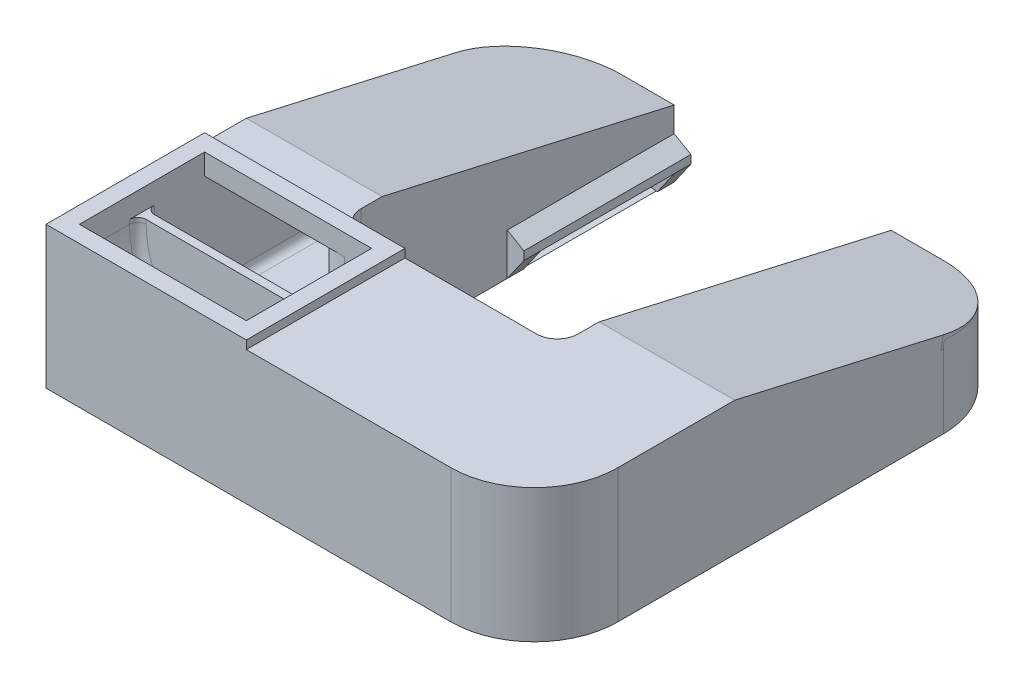
SolidWorks part; units mm, degrees
ref_plane "Front Plane" through (0, 0, 0) normal (0, 0, 1) x (1, 0, 0)
ref_plane "Top Plane" through (0, 0, 0) normal (0, 1, 0) x (1, 0, 0)
ref_plane "Right Plane" through (0, 0, 0) normal (1, 0, 0) x (0, 0, -1)
sketch "Sketch1" plane through (0, 0, 0) normal (0, 1, 0) x (1, 0, 0)
  line L0 (-13, 40) -> (-13, 0)
  line L1 (-13, 0) -> (13, 0)
  line L2 (13, 0) -> (13, 40)
  line L3 (13, 40) -> (19.25, 40)
  line L4 (29.25, 30) -> (29.25, -9)
  line L5 (19.25, -19) -> (-29.25, -19)
  line L6 (-29.25, -19) -> (-29.25, 30)
  line L7 (-19.25, 40) -> (-13, 40)
  arc A0 (19.25, 40) -> (29.25, 30) centre (19.25, 30) cw
  arc A1 (-29.25, 30) -> (-19.25, 40) centre (-19.25, 30) cw
  arc A2 (29.25, -9) -> (19.25, -19) centre (19.25, -9) cw
  point P11 (29.25, 40)
  point P14 (-29.25, 40)
  dimension "D7" = 10
  dimension "D8" = 10
  dimension "D1" = 26
  dimension "D2" = 13
  dimension "D3" = 40
  dimension "D4" = 16.25
  dimension "D5" = 16.25
  dimension "D6" = 19
extrude "Boss-Extrude1" add sketch "Sketch1" along normal blind 2
sketch "Sketch2" plane through (0, 2, 0) normal (0, 1, 0) x (1, 0, 0)
  line L0 (-29.25, 30) -> (-29.25, -19)
  line L1 (-29.25, -19) -> (19.25, -19)
  line L2 (-19.25, 40) -> (-13, 40)
  line L3 (-13, 40) -> (-13, 0)
  line L4 (-13, 0) -> (13, 0)
  line L5 (13, 0) -> (13, 40)
  line L6 (13, 40) -> (19.25, 40)
  line L7 (29.25, 30) -> (29.25, -9)
  line L8 (27.25, 30) -> (27.25, -9)
  line L9 (-27.25, -17) -> (19.25, -17)
  line L10 (-27.25, 30) -> (-27.25, -17)
  line L11 (-19.25, 38) -> (-15, 38)
  line L12 (-15, 38) -> (-15, -2)
  line L13 (-15, -2) -> (15, -2)
  line L14 (15, -2) -> (15, 38)
  line L15 (15, 38) -> (19.25, 38)
  arc A0 (-19.25, 40) -> (-29.25, 30) centre (-19.25, 30) ccw
  arc A1 (19.25, -19) -> (29.25, -9) centre (19.25, -9) ccw
  arc A2 (19.25, 40) -> (29.25, 30) centre (19.25, 30) cw
  arc A3 (19.25, 38) -> (27.25, 30) centre (19.25, 30) cw
  arc A4 (19.25, -17) -> (27.25, -9) centre (19.25, -9) ccw
  arc A5 (-19.25, 38) -> (-27.25, 30) centre (-19.25, 30) ccw
  dimension "D1" = 2
extrude "Boss-Extrude2" add sketch "Sketch2" along normal blind 14
sketch "Sketch3" plane through (0, 2, 0) normal (0, 1, 0) x (1, 0, 0)
  line L0 (-27.25, 30) -> (-27.25, -17) construction
  line L1 (-27.25, -9) -> (-7.25, -9)
  line L11 (15, -2) -> (-15, -2) construction
  line L15 (-7.25, -9) -> (-7.25, -2)
  line L16 (-27.25, -10) -> (-6.25, -10)
  line L18 (-7.25, -2) -> (15, -2)
  line L19 (-27.25, -9) -> (-27.25, -10)
  line L21 (-6.25, -10) -> (7, -10)
  line L23 (-27.25, -17) -> (19.25, -17) construction
  arc A0 (15, -2) -> (7, -10) centre (7, -2) cw
  dimension "D1" = 20
  dimension "D2" = 7
  dimension "D4" = 1
  dimension "D5" = 1
extrude "Boss-Extrude3" add sketch "Sketch3" along normal up to surface (14 mm away) up to face at (1.9383, 16, -15.9156)
fillet "Fillet1" radius 7 2 edges at (-7.25, 2, 5.5) (-17.25, 2, 9)
fillet "Fillet9" radius 12 1 edges at (-27.25, 2, 13.5)
fillet "Fillet6" radius 2.5 2 edges at (13, 8, 0) (-13, 8, 0)
fillet "Fillet7" radius 4.5 1 edges at (-15, 9, 2)
fillet "Fillet8" radius 1 22 edges at (-7.25, 12.5, 2) (-8.1161, 5.6273, 2) (-12.9756, 2.117, 1.2579) (12.6569, 2, 7.6569) (15, 2, -18) (17.125, 2, -38) (24.9069, 2, -35.6569) (27.25, 2, -10.5) (24.9069, 2, 14.6569) (2, 2, 17) (-4.125, 2, 10) (-24.9069, 2, -35.6569) (-17.125, 2, -38) (-15, 2, -20.25) (-14.8084, 2, -1.201) (-27.25, 2, -14) (-27.25, 15, 17) (-23.7353, 5.5147, 17) (-27.25, 15, 10) (-23.7353, 5.5147, 10) (-27.25, 12.5, 9) (-27.25, 4.0503, 6.9497)
sketch "Sketch4" plane through (0, 16, 0) normal (0, 1, 0) x (1, 0, 0)
  line L1 (-10.5, -2) -> (-27.25, -2)
  line L2 (-7.25, -10) -> (-7.25, -17)
  line L3 (-26.25, -17) -> (19.25, -17) construction
  line L6 (-15, 2.5) -> (-15, 38)
  line L7 (-15, 38) -> (-19.25, 38)
  line L8 (-27.25, 30) -> (-27.25, -2)
  line L9 (-7.25, -17) -> (19.25, -17)
  line L10 (27.25, -9) -> (27.25, 30)
  line L11 (19.25, 38) -> (15, 38)
  line L12 (15, 38) -> (15, -2)
  line L13 (7, -10) -> (-7.25, -10)
  line L14 (-26.25, -10) -> (7, -10) construction
  line L15 (-7.25, -3) -> (-7.25, -9) construction
  arc A1 (7, -10) -> (15, -2) centre (7, -2) ccw
  arc A2 (-19.25, 38) -> (-27.25, 30) centre (-19.25, 30) ccw
  arc A3 (19.25, 38) -> (27.25, 30) centre (19.25, 30) cw
  arc A4 (19.25, -17) -> (27.25, -9) centre (19.25, -9) ccw
  arc A6 (-15, 2.5) -> (-10.5, -2) centre (-10.5, 2.5) ccw
  arc A7 (-13.5682, -0.7918) -> (-10.5, -2) centre (-10.5, 2.5) ccw construction
extrude "Boss-Extrude4" add sketch "Sketch4" against normal blind 1.5
sketch "Sketch5" plane through (0, 16, 0) normal (0, 1, 0) x (1, 0, 0)
  line L0 (19.25, -17) -> (-15.25, -17) construction
  line L1 (-27.25, -2) -> (-7.25, -2)
  line L2 (-27.25, -2) -> (-27.25, -17)
  line L3 (-27.25, -17) -> (-7.25, -17)
  line L4 (-7.25, -2) -> (-7.25, -17)
  line L5 (-7.25, -10) -> (-7.25, -17) construction
extrude "Cut-Extrude1" cut sketch "Sketch5" against normal blind 1.5
sketch "Sketch6" plane through (0, 16, 0) normal (0, 1, 0) x (1, 0, 0)
  line L0 (-29.25, -19) -> (19.25, -19) construction
  line L1 (-27.25, -17) -> (-7.25, -17)
  line L2 (-27.25, -17) -> (-27.25, -2)
  line L3 (-27.25, -2) -> (-7.25, -2)
  line L4 (-7.25, -17) -> (-7.25, -2)
  line L5 (-5.25, -19) -> (-29.25, -19)
  line L6 (-5.25, -19) -> (-5.25, 0)
  line L7 (-5.25, 0) -> (-29.25, 0)
  line L8 (-29.25, -19) -> (-29.25, 0)
  dimension "D1" = 2
  dimension "D2" = 2
  dimension "D3" = 2
extrude "Boss-Extrude5" add sketch "Sketch6" along normal blind 1
ref_plane "Plane1" through (0, 0, -30) normal (0, 0, -1) x (-1, 0, 0)
sketch "Sketch7" plane through (0, 0, -30) normal (0, 0, -1) x (-1, 0, 0)
  line L0 (-13, 2) -> (0, 0) construction
  line L1 (-13, 0) -> (-13, 16) construction
  line L2 (0, 0) -> (13, 2) construction
  line L3 (13, 16) -> (13, 0) construction
  line L4 (-19.25, 0) -> (-13, 0) construction
  line L5 (10.5, 0) -> (13, 0) construction
  line L6 (19.25, 0) -> (29.25, 0) construction
  line L7 (26.1529, 2) -> (8.6205, -0.6973)
  line L8 (8.6205, -0.6973) -> (8.0123, 3.2562)
  line L9 (8.0123, 3.2562) -> (25.5447, 5.9535)
  line L10 (25.5447, 5.9535) -> (26.1529, 2)
  dimension "D1" = 2
  dimension "D2" = 2
  dimension "D3" = 2
  dimension "D4" = 4
  dimension "D5" = 2
extrude "Cut-Extrude2" cut sketch "Sketch7" against normal blind 8
sketch "Sketch9" plane through (-13, 0, 0) normal (1, 0, 0) x (0, 0, -1)
  line L0 (5, 16) -> (40, 8)
  line L1 (2.5, 16) -> (40, 16) construction
  line L2 (40, 16) -> (40, 0) construction
  line L3 (40, 8) -> (40, 16)
  line L4 (40, 16) -> (5, 16)
  dimension "D1" = 35
extrude "Cut-Extrude3" cut sketch "Sketch9" against normal through all
sketch "Sketch10" plane through (0, 16.2917, -3.7238) normal (0, 0.9749, -0.2228) x (1, 0, 0)
  line L0 (-29.25, 26.9538) -> (-29.25, 1.3091)
  line L1 (-29.25, 1.3091) -> (-13, 1.3091)
  line L2 (-13, 1.3091) -> (-13, 37.2117)
  line L3 (-13, 1.3091) -> (-13, 37.2117) construction
  line L4 (-13, 37.2117) -> (-19.25, 37.2117)
  line L5 (-13, 37.2117) -> (-13, 38.9943) construction
  arc A1 (-19.25, 37.2117) -> (-29.25, 26.9538) centre (-19.1042, 27.0664) ccw
  ellipse E0 centre (-19.25, 26.9538) end of major axis (-19.25, 37.2117) minor radius 10 (-19.25, 37.2117) -> (-29.25, 26.9538) ccw construction
extrude "Boss-Extrude6" add sketch "Sketch10" against normal blind 1.5
sketch "Sketch11" plane through (-0.3041, -1.9767, 0) normal (0.1521, 0.9884, 0) x (0.9884, -0.1521, 0)
  line L0 (-27.3893, 30) -> (-12.8488, 30)
  line L1 (-19.3893, 38) -> (-12.8488, 38)
  line L2 (-12.8488, 30) -> (-12.8488, 38)
  line L3 (-19.4823, 38) -> (-15.2817, 38) construction
  arc A0 (-27.3893, 30) -> (-19.3893, 38) centre (-19.3893, 30) cw
extrude "Cut-Extrude4" cut sketch "Sketch11" along normal blind 4
mirror "Mirror2" about plane through (0, 0, 0) normal (1, 0, 0) of "Cut-Extrude4", "Boss-Extrude6", "Cut-Extrude3", "Cut-Extrude2"
sketch "Sketch12" plane through (0, 0, -38) normal (0, 0, 1) x (1, 0, 0)
  line L0 (-13, 4.0235) -> (-11, 2.8688)
  line L1 (-11, 2.8688) -> (-11, 3.8688)
  line L2 (-11, 3.8688) -> (-13, 5.0235)
  line L3 (-13, 5.0235) -> (-13, 4.0235)
  line L4 (-13, 0) -> (-13, 4.0235) construction
  dimension "D1" = 2
  dimension "D2" = 1
  dimension "D3" = 60
extrude "Boss-Extrude7" add sketch "Sketch12" along normal up to surface (16 mm away) up to face at (-15.8713, 2.1639, -22)
sketch "Sketch13" plane through (0, 0, -38) normal (0, 0, -1) x (-1, 0, 0)
  line L0 (11, 3.8688) -> (11, 2.8688)
  line L1 (11, 2.8688) -> (11, 3.8688) construction
  line L2 (11, 2.8688) -> (13, 0)
  line L3 (13, 0) -> (13, 5.0235)
  line L4 (13, 16) -> (13, 0) construction
  line L5 (11, 3.8688) -> (13, 5.0235) construction
  line L6 (13, 5.0235) -> (11, 3.8688)
  line L7 (13, 4.0235) -> (11, 2.8688) construction
extrude "Boss-Extrude8" add sketch "Sketch13" along normal blind 2
sketch "Sketch14" plane through (0, 0, -22) normal (0, 0, 1) x (1, 0, 0)
  line L0 (-13, 5.0235) -> (-13, 0)
  line L1 (-13, 0) -> (-11, 2.8688)
  line L2 (-11, 2.8688) -> (-11, 3.8688)
  line L3 (-11, 3.8688) -> (-13, 5.0235)
extrude "Boss-Extrude9" add sketch "Sketch14" along normal blind 2
mirror "Mirror3" about plane through (0, 0, 0) normal (1, 0, 0) of "Boss-Extrude8", "Boss-Extrude9", "Boss-Extrude7"
